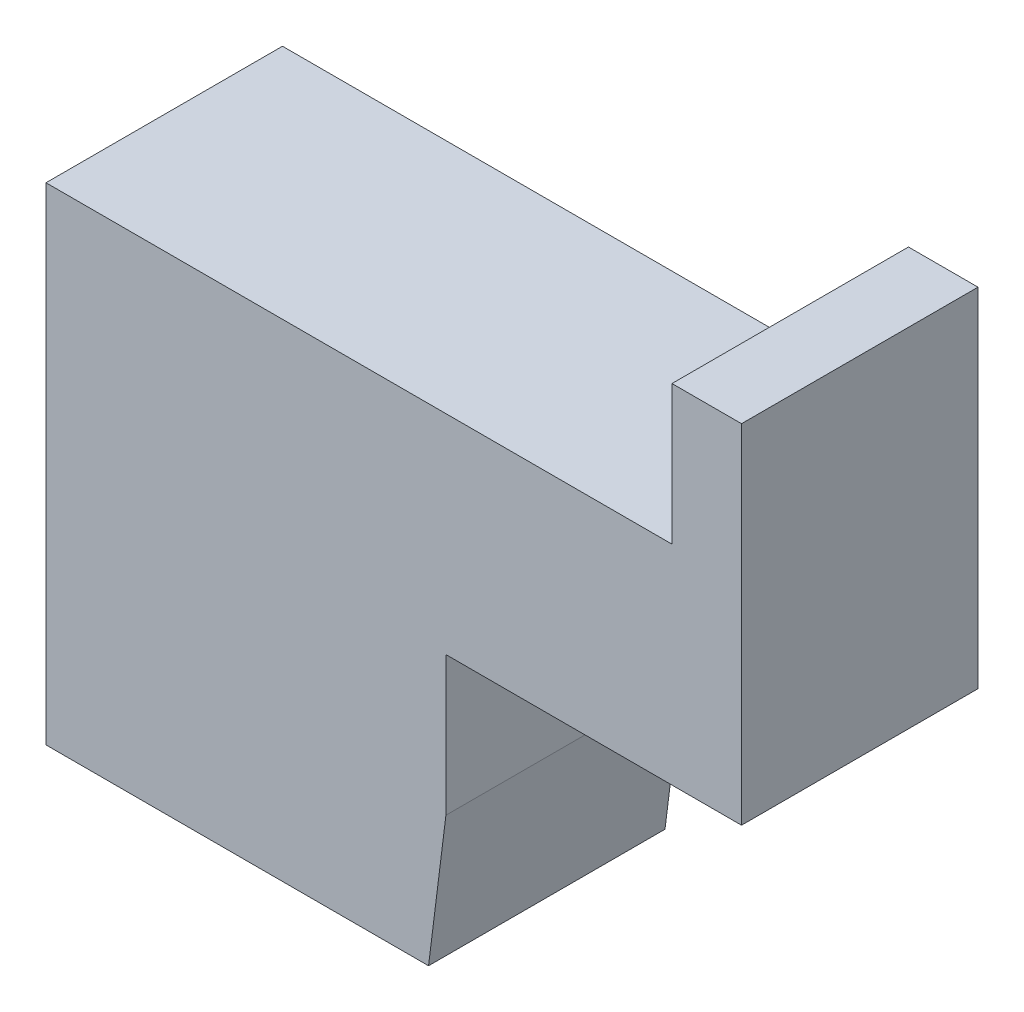
SolidWorks part; units mm, degrees
ref_plane "Front Plane" through (0, 0, 0) normal (0, 0, 1) x (1, 0, 0)
ref_plane "Top Plane" through (0, 0, 0) normal (0, 1, 0) x (1, 0, 0)
ref_plane "Right Plane" through (0, 0, 0) normal (1, 0, 0) x (0, 0, -1)
sketch "Sketch1" plane through (0, 0, 0) normal (0, 0, 1) x (1, 0, 0)
  line L0 (23.9819, 10.6109) -> (-16.0181, 10.6109)
  line L1 (-76.0181, 40.6109) -> (13.9819, 40.6109)
  line L2 (-76.0181, 40.6109) -> (-76.0181, 10.6109)
  line L3 (-16.0181, 10.6109) -> (23.9819, 10.6109)
  line L4 (23.9819, 40.6109) -> (23.9819, 10.6109)
  line L5 (-18.5181, -9.3891) -> (-18.5181, 10.6109)
  line L6 (-18.5181, 10.6109) -> (-16.0181, 10.6109)
  line L8 (-76.0181, 10.6109) -> (-76.0181, -29.3891)
  line L9 (-76.0181, -29.3891) -> (-21.0181, -29.3891)
  line L11 (-18.5181, -9.3891) -> (-21.0181, -29.3891)
  line L16 (23.9819, 40.6109) -> (23.9819, 60.6109)
  line L17 (23.9819, 60.6109) -> (13.9819, 60.6109)
  line L18 (13.9819, 40.6109) -> (13.9819, 60.6109)
  point P0 (-26.0181, 25.6109)
  dimension "D1" = 100
  dimension "D2" = 30
  dimension "D3" = 40
  dimension "D4" = 55
extrude "Boss-Extrude1" add sketch "Sketch1" along normal blind 34 contours L18 L1 L2 L8 L9 L11 L0 L4 L16 L17 region at (-33.3316, 12.0416, 0)
